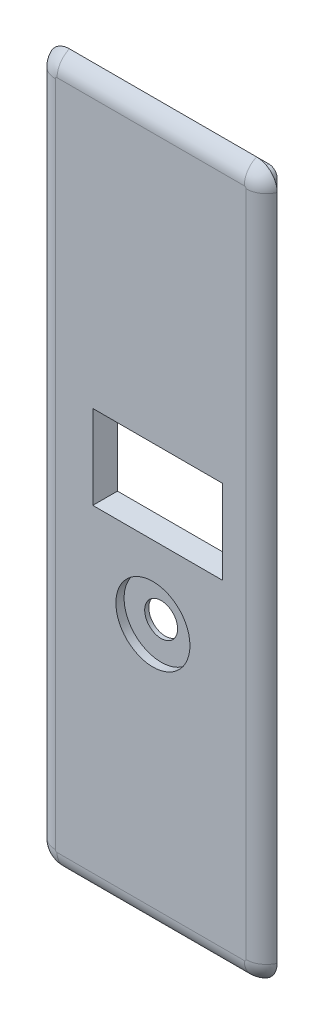
SolidWorks part; units mm, degrees
ref_plane "Plan de face" through (0, 0, 0) normal (0, 0, 1) x (1, 0, 0)
ref_plane "Plan de dessus" through (0, 0, 0) normal (0, 1, 0) x (1, 0, 0)
ref_plane "Plan de droite" through (0, 0, 0) normal (1, 0, 0) x (0, 0, -1)
sketch "Esquisse1" plane through (0, 0, 0) normal (0, 0, 1) x (1, 0, 0)
  line L0 (24.74, -69.15) -> (24.74, 93.04) construction
  line L1 (-22.74, -71.15) -> (22.74, -71.15) construction
  line L2 (-24.74, 93.04) -> (-24.74, -69.15) construction
  line L3 (22.74, 95.04) -> (-22.74, 95.04) construction
  line L4 (24.74, -69.15) -> (24.74, 93.04)
  line L5 (-22.74, -71.15) -> (22.74, -71.15)
  line L6 (-24.74, 93.04) -> (-24.74, -69.15)
  line L7 (22.74, 95.04) -> (-22.74, 95.04)
  line L12 (21.74, 92.04) -> (-21.74, 92.04)
  line L13 (-21.74, 92.04) -> (-21.74, -68.15)
  line L14 (-21.74, -68.15) -> (21.74, -68.15)
  line L15 (21.74, -68.15) -> (21.74, 92.04)
  arc A0 (22.74, -71.15) -> (24.74, -69.15) centre (22.74, -69.15) ccw construction
  arc A1 (-24.74, -69.15) -> (-22.74, -71.15) centre (-22.74, -69.15) ccw construction
  arc A2 (24.74, 93.04) -> (22.74, 95.04) centre (22.74, 93.04) ccw construction
  arc A3 (-22.74, 95.04) -> (-24.74, 93.04) centre (-22.74, 93.04) ccw construction
  arc A4 (22.74, -71.15) -> (24.74, -69.15) centre (22.74, -69.15) ccw
  arc A5 (-24.74, -69.15) -> (-22.74, -71.15) centre (-22.74, -69.15) ccw
  arc A6 (24.74, 93.04) -> (22.74, 95.04) centre (22.74, 93.04) ccw
  arc A7 (-22.74, 95.04) -> (-24.74, 93.04) centre (-22.74, 93.04) ccw
  arc A12 (-21.74, 92.04) -> (-21.74, 92.04) centre (-21.74, 92.04) ccw
  arc A13 (-21.74, -68.15) -> (-21.74, -68.15) centre (-21.74, -68.15) ccw
  arc A14 (21.74, -68.15) -> (21.74, -68.15) centre (21.74, -68.15) ccw
  arc A15 (21.74, 92.04) -> (21.74, 92.04) centre (21.74, 92.04) ccw
  dimension "D1" = 3
extrude "Boss.-Extru.1" add sketch "Esquisse1" against normal blind 3
sketch "Esquisse2" plane through (0, 0, 0) normal (0, 0, 1) x (1, 0, 0)
  line L4 (-22.74, -74.15) -> (22.74, -74.15)
  line L5 (27.74, -69.15) -> (27.74, 93.04)
  line L6 (22.74, 98.04) -> (-22.74, 98.04)
  line L7 (-27.74, 93.04) -> (-27.74, -69.15)
  line L8 (-22.74, -74.15) -> (22.74, -74.15)
  line L9 (27.74, -69.15) -> (27.74, 93.04)
  line L10 (22.74, 98.04) -> (-22.74, 98.04)
  line L11 (-27.74, 93.04) -> (-27.74, -69.15)
  circle A0 centre (0.548, -9.9) radius 4
  arc A4 (22.74, -74.15) -> (27.74, -69.15) centre (22.74, -69.15) ccw
  arc A5 (27.74, 93.04) -> (22.74, 98.04) centre (22.74, 93.04) ccw
  arc A6 (-22.74, 98.04) -> (-27.74, 93.04) centre (-22.74, 93.04) ccw
  arc A7 (-27.74, -69.15) -> (-22.74, -74.15) centre (-22.74, -69.15) ccw
  arc A8 (22.74, -74.15) -> (27.74, -69.15) centre (22.74, -69.15) ccw
  arc A9 (27.74, 93.04) -> (22.74, 98.04) centre (22.74, 93.04) ccw
  arc A10 (-22.74, 98.04) -> (-27.74, 93.04) centre (-22.74, 93.04) ccw
  arc A11 (-27.74, -69.15) -> (-22.74, -74.15) centre (-22.74, -69.15) ccw
  dimension "D2" = 8
  dimension "D1" = 0
extrude "Boss.-Extru.2" add sketch "Esquisse2" along normal blind 3
sketch "Esquisse3" plane through (0, 0, 3) normal (0, 0, 1) x (1, 0, 0)
  line L8 (14.4404, 10.809) -> (-11.0596, 10.809) construction
  line L9 (-11.0596, 25.209) -> (-11.0596, 10.809) construction
  line L10 (14.4404, 25.209) -> (-11.0596, 25.209) construction
  line L11 (14.4404, 25.209) -> (14.4404, 10.809) construction
  line L12 (14.4404, 10.809) -> (-11.0596, 10.809)
  line L13 (-11.0596, 25.209) -> (-11.0596, 10.809)
  line L14 (14.4404, 25.209) -> (-11.0596, 25.209)
  line L15 (14.4404, 25.209) -> (14.4404, 10.809)
extrude "Enlèv. mat.-Extru.1" cut sketch "Esquisse3" against normal up to next
chamfer "Chanfrein1" distance 3 angle 45 4 edges at (14.4404, 18.009, 3) (1.6904, 10.809, 3) (-11.0596, 18.009, 3) (1.6904, 25.209, 3)
fillet "Congé1" radius 5 8 edges at (-27.74, 11.945, 3) (-26.2755, 96.5755, 3) (0, 98.04, 3) (26.2755, 96.5755, 3) (27.74, 11.945, 3) (26.2755, -72.6855, 3) (0, -74.15, 3) (-26.2755, -72.6855, 3)
sketch "Esquisse4" plane through (0, 0, 3) normal (0, 0, 1) x (1, 0, 0)
  circle A0 centre (0.548, -9.9) radius 9
  dimension "D1" = 18
extrude "Enlèv. mat.-Extru.2" cut sketch "Esquisse4" against normal blind 2
